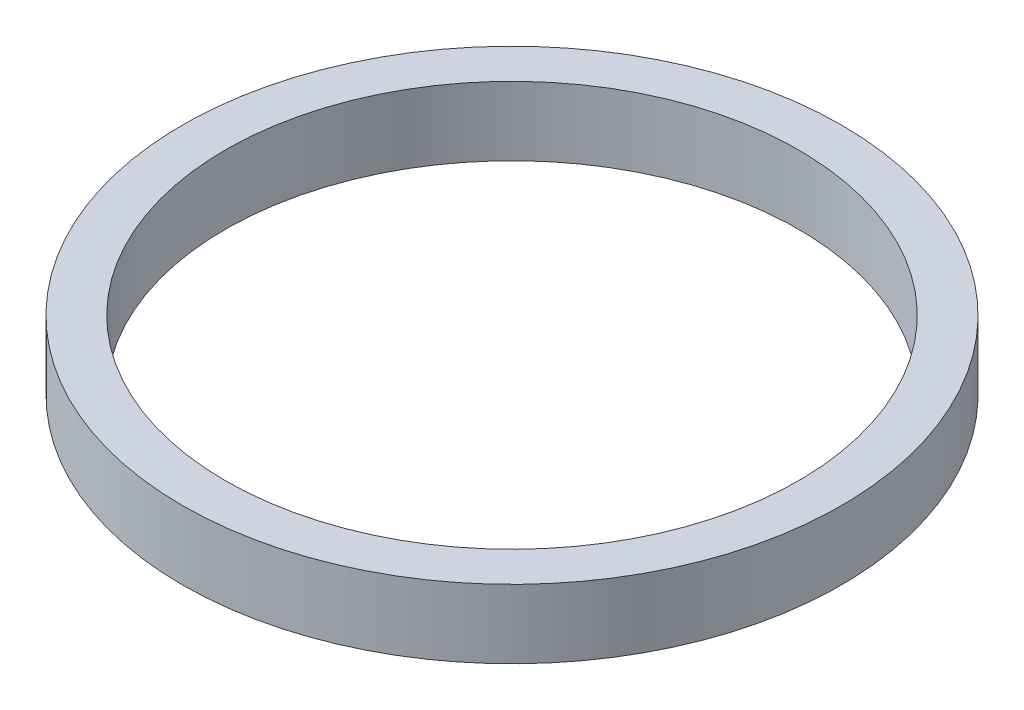
SolidWorks part; units mm, degrees
ref_plane "Front Plane" through (0, 0, 0) normal (0, 0, 1) x (1, 0, 0)
ref_plane "Top Plane" through (0, 0, 0) normal (0, 1, 0) x (1, 0, 0)
ref_plane "Right Plane" through (0, 0, 0) normal (1, 0, 0) x (0, 0, -1)
sketch "Sketch1" plane through (0, 0, 0) normal (0, 1, 0) x (1, 0, 0)
  circle A0 centre (0, 0) radius 57.5
  dimension "FLANGE_OD" = 115
extrude "Boss-Extrude1" add sketch "Sketch1" along normal blind 12
sketch "Sketch2" plane through (0, 0, 0) normal (0, 1, 0) x (1, 0, 0)
  circle A0 centre (0, 0) radius 50
  dimension "BORE_D" = 100
extrude "Cut-Extrude1" cut sketch "Sketch2" along normal through all
sketch "Sketch3" plane through (0, 12, 0) normal (0, 1, 0) x (1, 0, 0)
  circle A0 centre (0, 0) radius 27.2221 construction
  circle A1 centre (-27.2221, 0) radius 1.5
  dimension "BOLT_D" = 3
  dimension "BOLT_PCD" = 54.4441
extrude "Cut-Extrude2" cut sketch "Sketch3" against normal blind 10.0052 rebuild error yes
pattern_circular "CirPattern1" count 3 over 360 rebuild error yes
